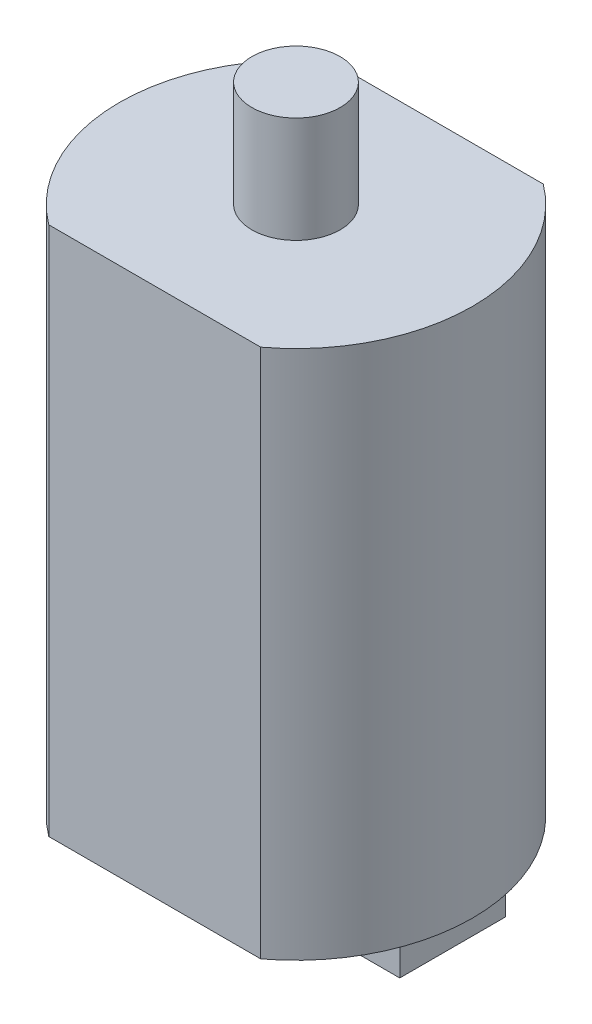
SolidWorks part; units mm, degrees
ref_plane "Front" through (0, 0, 0) normal (0, 0, 1) x (1, 0, 0)
ref_plane "Top" through (0, 0, 0) normal (0, 1, 0) x (1, 0, 0)
ref_plane "Right" through (0, 0, 0) normal (1, 0, 0) x (0, 0, -1)
sketch "Sketch1" plane through (0, 0, 0) normal (0, 1, 0) x (1, 0, 0)
  line L0 (-3, 4) -> (3, 4)
  line L1 (-3, -4) -> (3, -4)
  line L2 (-3.4375, 0) -> (3.4375, 0) construction
  line L4 (-2.4375, -1.5) -> (-4.4375, -1.5)
  line L5 (-2.4375, -1.5) -> (-2.4375, 1.5)
  line L6 (-2.4375, 1.5) -> (-4.4375, 1.5)
  line L7 (-4.4375, -1.5) -> (-4.4375, 1.5)
  line L8 (-2.4375, -1.5) -> (-4.4375, 1.5) construction
  line L9 (-2.4375, 1.5) -> (-4.4375, -1.5) construction
  line L10 (4.4375, -1.5) -> (2.4375, -1.5)
  line L11 (4.4375, -1.5) -> (4.4375, 1.5)
  line L12 (4.4375, 1.5) -> (2.4375, 1.5)
  line L13 (2.4375, -1.5) -> (2.4375, 1.5)
  line L14 (4.4375, -1.5) -> (2.4375, 1.5) construction
  line L15 (4.4375, 1.5) -> (2.4375, -1.5) construction
  circle A0 centre (0, 0) radius 5
  circle A1 centre (0, 0) radius 2
  circle A2 centre (0, 0) radius 1.25
  dimension "D1" = 10
  dimension "D6" = 4
  dimension "D7" = 2.5
  dimension "D2" = 8
  dimension "D3" = 3
  dimension "D4" = 2
  dimension "D5" = 4.875
extrude "Boss-Extrude1" add sketch "Sketch1" along normal blind 15 contours L1 A0 L0 A1 L10 L13 L12 L11 L4 L7 L6 L5 | L7 L4 L5 L6 | A1 A2 | A2 | L13 L10 L11 L12 region at (0, 0, -3.8719) region at (-3.4375, 0, 0) region at (3.4375, 0, 0) region at (-1.9434, 0, 0) region at (0, 0, 0)
extrude "Boss-Extrude2" add sketch "Sketch1<3>" against normal blind 1 contours L7 L4 L5 L6 | L13 L10 L11 L12 | A1 A2 | A2 region at (-3.4375, 0, 0) region at (3.4375, 0, 0) region at (-1.9434, 0, 0) region at (0, 0, 0)
sketch "Sketch1<3>" plane through (0, 0, 0) normal (0, 1, 0) x (1, 0, 0) same geometry as "Sketch1"
extrude "Boss-Extrude3" add sketch "Sketch1<4>" along normal blind 3 from surface contours A2 region at (0, 0, 0) starting at face at (0, 15, 0)
sketch "Sketch1<4>" plane through (0, 0, 0) normal (0, 1, 0) x (1, 0, 0) same geometry as "Sketch1"
